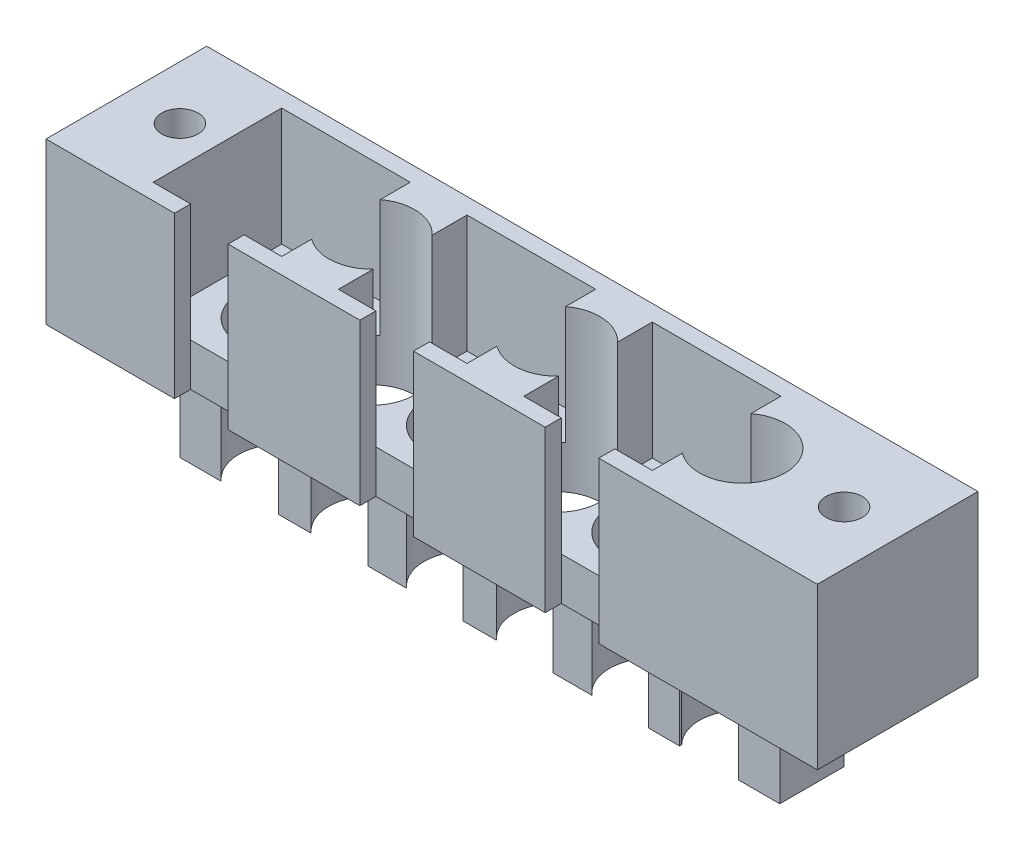
SolidWorks part; units mm, degrees
ref_plane "Front Plane" through (0, 0, 0) normal (0, 0, 1) x (1, 0, 0)
ref_plane "Top Plane" through (0, 0, 0) normal (0, 1, 0) x (1, 0, 0)
ref_plane "Right Plane" through (0, 0, 0) normal (1, 0, 0) x (0, 0, -1)
sketch "Sketch1" plane through (0, 0, 0) normal (0, 1, 0) x (1, 0, 0)
  line L0 (55.3347, -24.7724) -> (55.3347, -9.7724)
  line L1 (-16.6653, -9.7724) -> (55.3347, -9.7724)
  line L2 (55.3347, -24.7724) -> (-16.6653, -24.7724)
  line L3 (-4.6653, -23.7724) -> (-4.6653, -24.7724)
  line L4 (0.3347, -23.7724) -> (0.3347, -24.7724)
  line L5 (12.6347, -23.7724) -> (12.6347, -24.7724)
  line L6 (17.6347, -23.7724) -> (17.6347, -24.7724)
  line L7 (29.9347, -23.7724) -> (29.9347, -24.7724)
  line L8 (-16.6653, -9.7724) -> (-16.6653, -24.7724)
  line L9 (34.9347, -23.7724) -> (34.9347, -24.7724)
  line L10 (-11.6653, -4.2724) -> (-11.6653, -30.2724) construction
  line L11 (50.3347, -4.2724) -> (50.3347, -30.2724) construction
  line L12 (-16.6653, -17.2724) -> (50.3347, -17.2724) construction
  circle A0 centre (-11.6653, -17.2724) radius 1.7
  circle A1 centre (50.3347, -17.2724) radius 1.7
  line B0 (-8.1653, -11.2724) -> (-8.1653, -23.2724)
  line B1 (3.8347, -23.2724) -> (3.8347, -11.2724)
  line B2 (3.8347, -11.2724) -> (-8.1653, -11.2724)
  line B3 (-8.1653, -23.2724) -> (3.8347, -23.2724)
  line B4 (-8.1653, -11.2724) -> (3.8347, -23.2724) construction
  line B5 (-8.1653, -23.2724) -> (3.8347, -11.2724) construction
  line B6 (-2.1653, -11.2724) -> (-2.1653, -23.2724) construction
  line B7 (4.3347, -10.7724) -> (-8.6653, -10.7724)
  line B8 (-8.6653, -10.7724) -> (-8.6653, -23.7724)
  line B9 (4.3347, -23.7724) -> (4.3347, -10.7724)
  line B10 (-8.6653, -23.7724) -> (-4.6653, -23.7724)
  line B11 (4.3347, -23.7724) -> (0.3347, -23.7724)
  line B12 (-4.6653, -23.7724) -> (-4.6653, -23.2724)
  line B13 (0.3347, -23.7724) -> (0.3347, -23.2724)
  circle B14 centre (-2.1653, -17.2724) radius 4
  line B15 (9.1347, -11.2724) -> (9.1347, -23.2724)
  line B16 (21.1347, -23.2724) -> (21.1347, -11.2724)
  line B17 (21.1347, -11.2724) -> (9.1347, -11.2724)
  line B18 (9.1347, -23.2724) -> (21.1347, -23.2724)
  line B19 (9.1347, -11.2724) -> (21.1347, -23.2724) construction
  line B20 (9.1347, -23.2724) -> (21.1347, -11.2724) construction
  line B21 (15.1347, -11.2724) -> (15.1347, -23.2724) construction
  line B22 (21.6347, -10.7724) -> (8.6347, -10.7724)
  line B23 (8.6347, -10.7724) -> (8.6347, -23.7724)
  line B24 (21.6347, -23.7724) -> (21.6347, -10.7724)
  line B25 (8.6347, -23.7724) -> (12.6347, -23.7724)
  line B26 (21.6347, -23.7724) -> (17.6347, -23.7724)
  line B27 (12.6347, -23.7724) -> (12.6347, -23.2724)
  line B28 (17.6347, -23.7724) -> (17.6347, -23.2724)
  circle B29 centre (15.1347, -17.2724) radius 4
  line B30 (26.4347, -11.2724) -> (26.4347, -23.2724)
  line B31 (38.4347, -23.2724) -> (38.4347, -11.2724)
  line B32 (38.4347, -11.2724) -> (26.4347, -11.2724)
  line B33 (26.4347, -23.2724) -> (38.4347, -23.2724)
  line B34 (26.4347, -11.2724) -> (38.4347, -23.2724) construction
  line B35 (26.4347, -23.2724) -> (38.4347, -11.2724) construction
  line B36 (32.4347, -11.2724) -> (32.4347, -23.2724) construction
  line B37 (38.9347, -10.7724) -> (25.9347, -10.7724)
  line B38 (25.9347, -10.7724) -> (25.9347, -23.7724)
  line B39 (38.9347, -23.7724) -> (38.9347, -10.7724)
  line B40 (25.9347, -23.7724) -> (29.9347, -23.7724)
  line B41 (38.9347, -23.7724) -> (34.9347, -23.7724)
  line B42 (29.9347, -23.7724) -> (29.9347, -23.2724)
  line B43 (34.9347, -23.7724) -> (34.9347, -23.2724)
  circle B44 centre (32.4347, -17.2724) radius 4
  dimension "D5" = 0
  dimension "D1" = 0
  dimension "D2" = 0
  dimension "D3" = 5
  dimension "D4" = 72
  dimension "D6" = 8
  dimension "D7" = 17.3
  dimension "D8" = 17.3
  dimension "D9" = 15
sketch_block_instance "Block10-1"
sketch_block "Block10" parameters "D1"=12
sketch_block_instance "Block10-2"
sketch_block_instance "Block10-3"
extrude "Boss-Extrude1" add sketch "Sketch1" along normal blind 4 contours B0 B3 B1 B2 B14 | B15 B18 B16 B17 B29 | B30 B33 B31 B32 B44 region at (32.4347, 0, 23.1026) region at (15.1347, 0, 23.1026) region at (-6.4153, 0, 23.1026)
extrude "Boss-Extrude2" add sketch "Sketch1<3>" along normal blind 15 contours L8 A0 | A1 | B13 B11 B9 B7 B8 B10 B12 B3 B0 B2 B1 | B28 B26 B24 B22 B23 B25 B27 B18 B15 B17 B16 | B43 B41 B39 B37 B38 B40 B42 B33 B30 B32 B31 region at (23.3959, 0, 17.0779) region at (35.1186, 0, 23.5224) region at (17.8186, 0, 23.5224) region at (-6.6653, 0, 23.5885)
sketch "Sketch1<3>" plane through (0, 0, 0) normal (0, 1, 0) x (1, 0, 0) same geometry as "Sketch1"
sketch "Sketch3" plane through (0, 0, 0) normal (0, -1, 0) x (1, 0, 0)
  text T0 "F10"
sketch "Sketch4" plane through (0, 15, 0) normal (0, 1, 0) x (1, 0, 0)
  line L0 (55.3347, -17.2724) -> (-16.6653, -17.2724) construction
  line L1 (55.3347, -24.7724) -> (55.3347, -9.7724) construction
  line L2 (-16.6653, -9.7724) -> (-16.6653, -24.7724) construction
  line L3 (-2.1653, -11.2724) -> (-2.1653, -23.2724) construction
  line L4 (3.8347, -11.2724) -> (-8.1653, -11.2724) construction
  line L5 (-4.6653, -23.2724) -> (0.3347, -23.2724) construction
  line L6 (15.1347, -11.2724) -> (15.1347, -23.2724) construction
  line L7 (21.1347, -11.2724) -> (9.1347, -11.2724) construction
  line L8 (12.6347, -23.2724) -> (17.6347, -23.2724) construction
  line L9 (32.4347, -11.2724) -> (32.4347, -23.2724) construction
  line L10 (38.4347, -11.2724) -> (26.4347, -11.2724) construction
  line L11 (29.9347, -23.2724) -> (34.9347, -23.2724) construction
  line L14 (3.7347, -10.7724) -> (3.7347, -9.7724)
  line L15 (-16.6653, -9.7724) -> (55.3347, -9.7724) construction
  line L16 (8.7347, -10.7724) -> (8.7347, -9.7724)
  line L17 (21.0347, -10.7724) -> (21.0347, -9.7724)
  line L18 (26.0347, -10.7724) -> (26.0347, -9.7724)
  line L19 (38.3347, -10.7724) -> (38.3347, -9.7724)
  line L20 (43.3347, -10.7724) -> (43.3347, -9.7724)
  line B0 (12.2347, -23.2724) -> (12.2347, -11.2724)
  line B1 (0.2347, -11.2724) -> (0.2347, -23.2724)
  line B2 (0.2347, -23.2724) -> (12.2347, -23.2724)
  line B3 (12.2347, -11.2724) -> (0.2347, -11.2724)
  line B4 (12.2347, -23.2724) -> (0.2347, -11.2724) construction
  line B5 (12.2347, -11.2724) -> (0.2347, -23.2724) construction
  line B6 (6.2347, -23.2724) -> (6.2347, -11.2724) construction
  line B7 (-0.2653, -23.7724) -> (12.7347, -23.7724)
  line B8 (12.7347, -23.7724) -> (12.7347, -10.7724)
  line B9 (-0.2653, -10.7724) -> (-0.2653, -23.7724)
  line B10 (12.7347, -10.7724) -> (8.7347, -10.7724)
  line B11 (-0.2653, -10.7724) -> (3.7347, -10.7724)
  line B12 (8.7347, -10.7724) -> (8.7347, -11.2724)
  line B13 (3.7347, -10.7724) -> (3.7347, -11.2724)
  circle B14 centre (6.2347, -17.2724) radius 4
  line B15 (29.5347, -23.2724) -> (29.5347, -11.2724)
  line B16 (17.5347, -11.2724) -> (17.5347, -23.2724)
  line B17 (17.5347, -23.2724) -> (29.5347, -23.2724)
  line B18 (29.5347, -11.2724) -> (17.5347, -11.2724)
  line B19 (29.5347, -23.2724) -> (17.5347, -11.2724) construction
  line B20 (29.5347, -11.2724) -> (17.5347, -23.2724) construction
  line B21 (23.5347, -23.2724) -> (23.5347, -11.2724) construction
  line B22 (17.0347, -23.7724) -> (30.0347, -23.7724)
  line B23 (30.0347, -23.7724) -> (30.0347, -10.7724)
  line B24 (17.0347, -10.7724) -> (17.0347, -23.7724)
  line B25 (30.0347, -10.7724) -> (26.0347, -10.7724)
  line B26 (17.0347, -10.7724) -> (21.0347, -10.7724)
  line B27 (26.0347, -10.7724) -> (26.0347, -11.2724)
  line B28 (21.0347, -10.7724) -> (21.0347, -11.2724)
  circle B29 centre (23.5347, -17.2724) radius 4
  line B30 (46.8347, -23.2724) -> (46.8347, -11.2724)
  line B31 (34.8347, -11.2724) -> (34.8347, -23.2724)
  line B32 (34.8347, -23.2724) -> (46.8347, -23.2724)
  line B33 (46.8347, -11.2724) -> (34.8347, -11.2724)
  line B34 (46.8347, -23.2724) -> (34.8347, -11.2724) construction
  line B35 (46.8347, -11.2724) -> (34.8347, -23.2724) construction
  line B36 (40.8347, -23.2724) -> (40.8347, -11.2724) construction
  line B37 (34.3347, -23.7724) -> (47.3347, -23.7724)
  line B38 (47.3347, -23.7724) -> (47.3347, -10.7724)
  line B39 (34.3347, -10.7724) -> (34.3347, -23.7724)
  line B40 (47.3347, -10.7724) -> (43.3347, -10.7724)
  line B41 (34.3347, -10.7724) -> (38.3347, -10.7724)
  line B42 (43.3347, -10.7724) -> (43.3347, -11.2724)
  line B43 (38.3347, -10.7724) -> (38.3347, -11.2724)
  circle B44 centre (40.8347, -17.2724) radius 4
  line M16 (3.8347, -11.2724) -> (3.8347, -23.2724)
  line M22 (9.1347, -23.2724) -> (9.1347, -11.2724)
  line M24 (21.1347, -11.2724) -> (21.1347, -23.2724)
  line M30 (26.4347, -23.2724) -> (26.4347, -11.2724)
  line M32 (38.4347, -11.2724) -> (38.4347, -23.2724)
  dimension "D1" = 0
  dimension "D2" = 0
  dimension "D3" = 0
  dimension "D4" = 8.4
  dimension "D5" = 8.4
  dimension "D6" = 8.4
  dimension "D7" = 14.5
  dimension "D8" = 14.5
sketch_block_instance "Block10-5"
sketch_block_instance "Block10-6"
sketch_block_instance "Block10-7"
extrude "Cut-Extrude1" cut sketch "Sketch4" against normal through all contours B14 M22 M16 | B29 M30 M24 | B44 M32 | B14 M16 | B14 M22 | B29 M24 | B29 M30 | B44 M32 region at (9.5804, 15, 17.2724) region at (6.4377, 15, 17.2724) region at (3.1823, 15, 17.2724) region at (26.8804, 15, 17.2724) region at (23.7377, 15, 17.2724) region at (20.4823, 15, 17.2724) region at (41.3415, 15, 17.2724) region at (37.7823, 15, 17.2724)
sketch "Sketch5" plane through (0, 0, 0) normal (0, -1, 0) x (1, 0, 0)
  line L0 (0.5568, 14.3415) -> (0.5568, 14.2724)
  line L1 (0.5568, 20.2724) -> (37.9809, 20.2724)
  line L5 (0.5568, 20.2724) -> (0.5568, 14.3415)
  line L23 (37.9809, 14.2724) -> (37.9809, 20.2724)
  line L26 (37.9809, 14.2724) -> (0.5568, 14.2724)
  line L27 (-4.3262, 20.6384) -> (-4.3262, 20.2724)
  line L28 (-4.3262, 20.2724) -> (-8.6681, 20.2724)
  line L29 (-8.6681, 20.2724) -> (-8.6681, 14.2724)
  line L30 (-8.6681, 14.2724) -> (-4.3262, 14.2724)
  line L31 (-4.3262, 14.2724) -> (-4.3262, 20.6384)
  line L32 (-16.6653, 17.2724) -> (55.3347, 17.2724) construction
  line L33 (-16.6653, 9.7724) -> (-16.6653, 24.7724) construction
  line L34 (55.3347, 24.7724) -> (55.3347, 9.7724) construction
  line L35 (47.3304, 17.2724) -> (47.3304, 20.2724)
  line L39 (47.3304, 14.2724) -> (47.3304, 17.2724)
  line L41 (44.3347, 14.2724) -> (47.3304, 14.2724)
  line L42 (47.3304, 20.2724) -> (44.3347, 20.2724)
  line L43 (44.3347, 14.2724) -> (42.2928, 14.2724)
  line L44 (42.2928, 14.2724) -> (42.2928, 20.2724)
  line L45 (42.2928, 20.2724) -> (44.3347, 20.2724)
  line L46 (-2.1653, 21.2724) -> (-2.1653, 13.2724) construction
  line L47 (40.8347, 21.2724) -> (40.8347, 13.2724) construction
  circle A0 centre (-2.1653, 17.2724) radius 4 construction
  circle A1 centre (6.2347, 17.2724) radius 4
  circle A2 centre (-2.1653, 17.2724) radius 4
  circle A3 centre (15.1347, 17.2724) radius 4
  circle A4 centre (23.5347, 17.2724) radius 4
  circle A5 centre (32.4347, 17.2724) radius 4
  circle A6 centre (40.8347, 17.2724) radius 4
  circle M18 centre (6.2347, 17.2724) radius 4
  circle M19 centre (23.5347, 17.2724) radius 4
  circle M20 centre (40.8347, 17.2724) radius 4
  circle M37 centre (-2.1653, 17.2724) radius 4
  circle M40 centre (15.1347, 17.2724) radius 4
  circle M41 centre (32.4347, 17.2724) radius 4
  dimension "D1" = 6
  dimension "D2" = 3
  dimension "D3" = 6
  dimension "D4" = 3
  dimension "D5" = 14.5
  dimension "D6" = 14.5
extrude "Cut-Extrude2" cut sketch "Sketch3" against normal blind 1
extrude "Boss-Extrude4" add sketch "Sketch5" along normal blind 9 contours L29 L30 L28 M37 | L26 L1 L5 L0 M18 M37 | L26 L1 M40 M18 | L26 L1 M19 M40 | L26 L1 M41 M19 | L26 L23 L1 M20 M41 | L45 L43 L41 L39 L35 L42 M20 region at (2.0358, 0, 17.2724) region at (-7.1828, 0, 17.2724) region at (10.6847, 0, 17.2724) region at (19.3347, 0, 17.2724) region at (27.9847, 0, 17.2724) region at (36.627, 0, 17.2724) region at (45.8486, 0, 17.2724)
